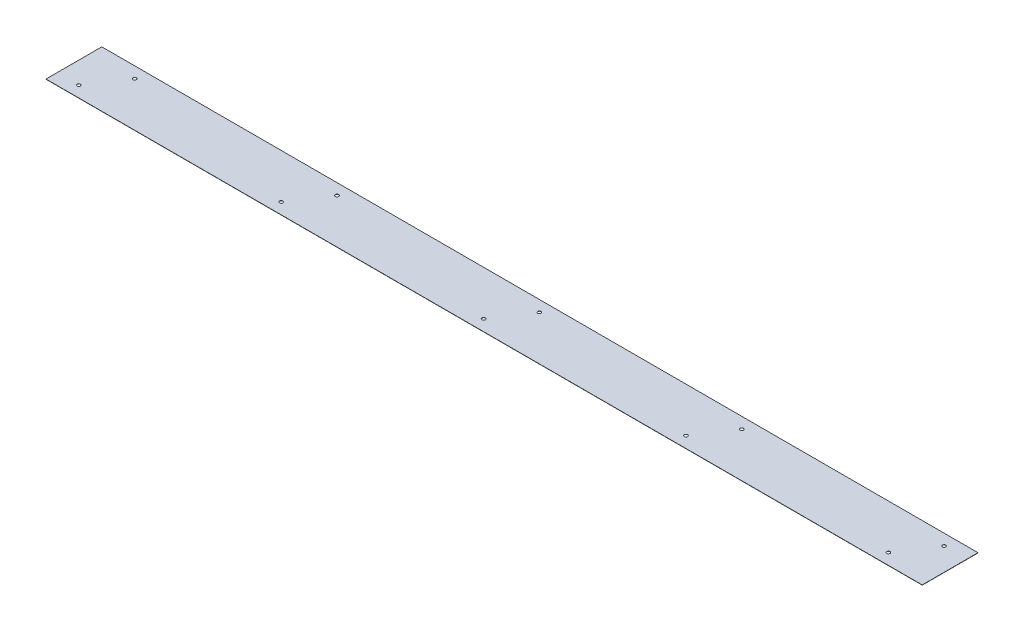
SolidWorks part; units mm, degrees
material "1060 Alloy"
ref_plane "Front Plane" through (0, 0, 0) normal (0, 0, 1) x (1, 0, 0)
ref_plane "Top Plane" through (0, 0, 0) normal (0, 1, 0) x (1, 0, 0)
ref_plane "Right Plane" through (0, 0, 0) normal (1, 0, 0) x (0, 0, -1)
sketch "Sketch1" plane through (0, 0, 0) normal (0, 1, 0) x (1, 0, 0)
  line L1 (0, 0) -> (785.4, 0)
  line L2 (0, 0) -> (0, 50)
  line L3 (0, 50) -> (785.4, 50)
  line L4 (785.4, 0) -> (785.4, 50)
  dimension "D1" = 785.4
  dimension "D2" = 50
extrude "Boss-Extrude1" add sketch "Sketch1" along normal blind 0.2
sketch "Sketch2" plane through (0, 0, 0) normal (0, 1, 0) x (1, 0, 0)
  line L0 (0, 25) -> (785.4, 25) construction
  line L1 (0, 50) -> (0, 0) construction
  line L2 (785.4, 0) -> (785.4, 50) construction
  line L3 (0, 0) -> (785.4, 0) construction
  circle A0 centre (19.4377, 10) radius 1.5
  circle A1 centre (39.4377, 40) radius 1.5
  circle A2 centre (200.8377, 10) radius 1.5
  circle A3 centre (220.8377, 40) radius 1.5
  circle A4 centre (382.2377, 10) radius 1.5
  circle A5 centre (402.2377, 40) radius 1.5
  circle A6 centre (563.6377, 10) radius 1.5
  circle A7 centre (583.6377, 40) radius 1.5
  circle A8 centre (745.0377, 10) radius 1.5
  circle A9 centre (765.0377, 40) radius 1.5
  dimension "D1" = 3
  dimension "D2" = 3
  dimension "D3" = 10
  dimension "D4" = 10
  dimension "D5" = 20
  dimension "D6" = 5
extrude "Cut-Extrude1" cut sketch "Sketch2" against normal blind 0.2 and the other way blind 0.2
